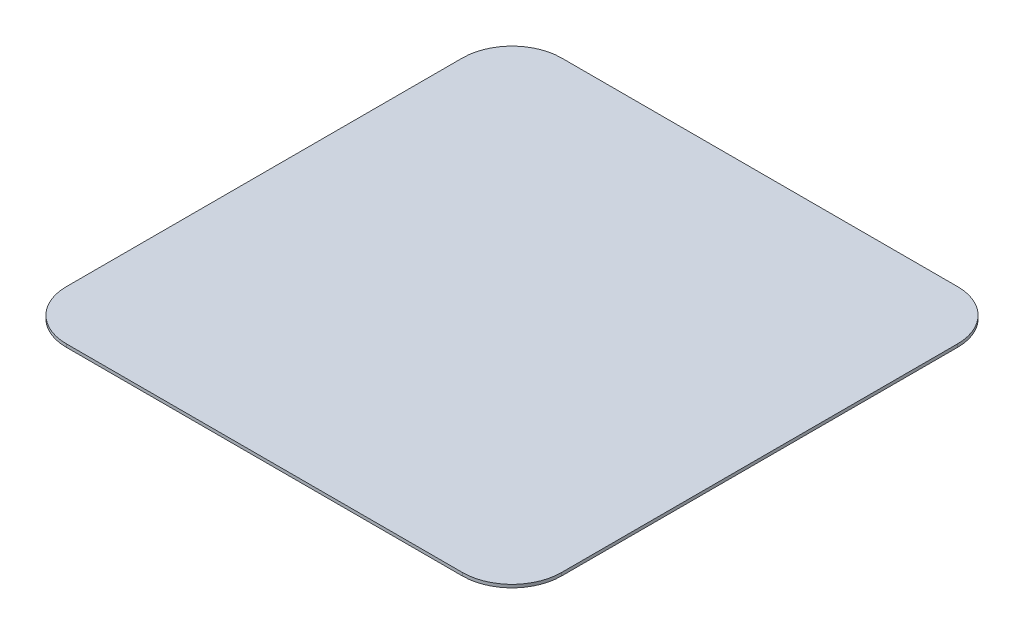
SolidWorks part; units mm, degrees
ref_plane "Front Plane" through (0, 0, 0) normal (0, 0, 1) x (1, 0, 0)
ref_plane "Top Plane" through (0, 0, 0) normal (0, 1, 0) x (1, 0, 0)
ref_plane "Right Plane" through (0, 0, 0) normal (1, 0, 0) x (0, 0, -1)
ref_plane "SheetPlane" through (0, 25.0193, 0) normal (0, 1, 0) x (1, 0, 0)
sketch "Sketch1" plane through (0, 25.0193, 0) normal (0, 1, 0) x (1, 0, 0)
  line L1 (-54.0192, -49.2656) -> (47.5808, -49.2656) construction
  line L2 (-66.7192, 65.0344) -> (-66.7192, -36.5656) construction
  line L3 (47.5808, 77.7344) -> (-54.0192, 77.7344) construction
  line L16 (60.2808, -36.5656) -> (60.2808, 65.0344)
  line L17 (-54.0192, -49.2656) -> (47.5808, -49.2656)
  line L18 (-66.7192, 65.0344) -> (-66.7192, -36.5656)
  line L19 (47.5808, 77.7344) -> (-54.0192, 77.7344)
  line L20 (60.2808, -36.5656) -> (60.2808, 65.0344) construction
  arc A0 (-54.0192, 77.7344) -> (-66.7192, 65.0344) centre (-54.0192, 65.0344) ccw construction
  arc A1 (-66.7192, -36.5656) -> (-54.0192, -49.2656) centre (-54.0192, -36.5656) ccw construction
  arc A2 (-54.0192, 77.7344) -> (-66.7192, 65.0344) centre (-54.0192, 65.0344) ccw
  arc A3 (47.5808, -49.2656) -> (60.2808, -36.5656) centre (47.5808, -36.5656) ccw construction
  arc A12 (47.5808, -49.2656) -> (60.2808, -36.5656) centre (47.5808, -36.5656) ccw
  arc A13 (60.2808, 65.0344) -> (47.5808, 77.7344) centre (47.5808, 65.0344) ccw construction
  arc A14 (60.2808, 65.0344) -> (47.5808, 77.7344) centre (47.5808, 65.0344) ccw
  arc A18 (-66.7192, -36.5656) -> (-54.0192, -49.2656) centre (-54.0192, -36.5656) ccw
extrude "MainBody" add sketch "Sketch1" along normal blind 0.7937
equation "\"SheetThickness\"= 0.03125in"
equation "\"D1@MainBody\" = \"SheetThickness\""
equation "\"SheetTolerance\"= 0.012in"
